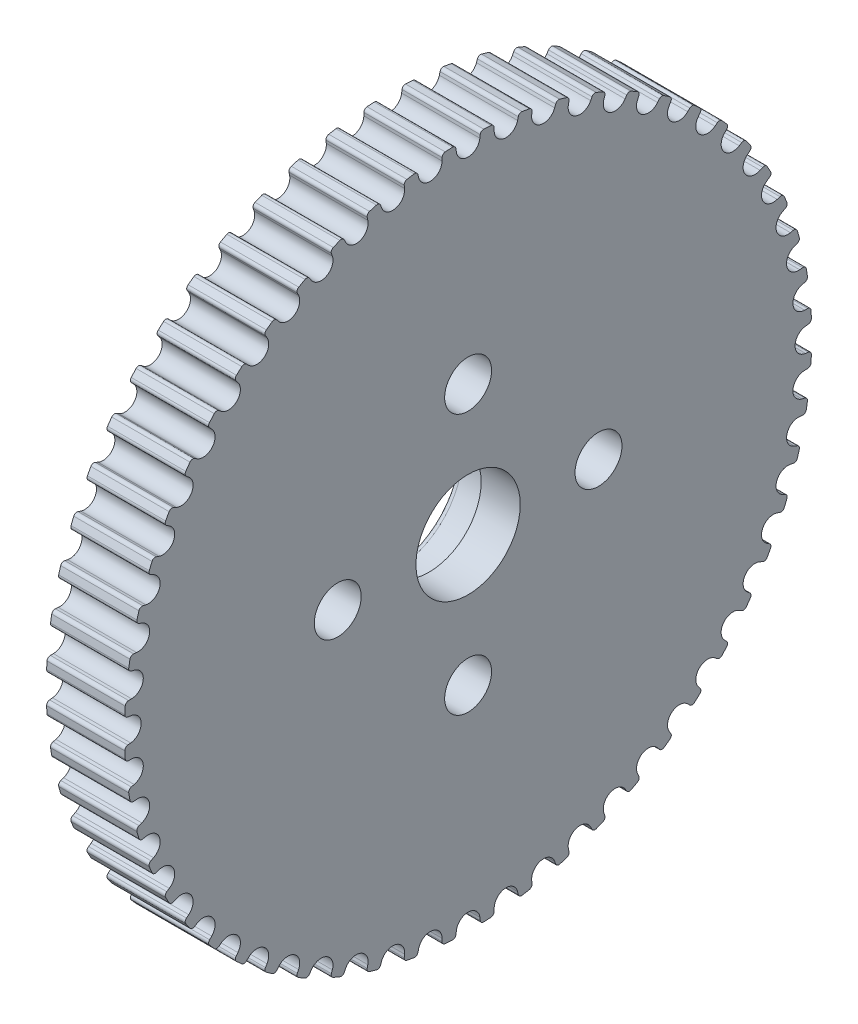
SolidWorks part; units mm, degrees
ref_plane "前视基准面" through (0, 0, 0) normal (0, 0, 1) x (1, 0, 0)
ref_plane "上视基准面" through (0, 0, 0) normal (0, 1, 0) x (1, 0, 0)
ref_plane "右视基准面" through (0, 0, 0) normal (1, 0, 0) x (0, 0, -1)
sketch "草图1" plane through (0, 0, 0) normal (0, 0, 1) x (1, 0, 0)
  line L0 (0, 0) -> (64.8368, 0) construction
  line L1 (0, 5.2718) -> (0, 26.359)
  line L2 (0, 26.359) -> (6, 26.359)
  line L3 (6, 26.359) -> (6, 10.5436)
  line L10 (6, 10.5436) -> (6, 0)
  line L11 (6, 0) -> (0, 0)
  line L12 (0, 0) -> (0, 5.2718)
  dimension "B" = 6
  dimension "da" = 52.718
revolve "旋转1" add sketch "草图1" angle 360 about L0
ref_axis "基准轴1" through (-0.45, 0, 0) along (1, 0, 0)
sketch "草图6" plane through (0, 0, 0) normal (1, 0, 0) x (0, 0, -1)
  line L0 (0, 0) -> (0, 30.6512) construction
  line L1 (0.9309, 26.1036) -> (0.9032, 25.8781)
  line L2 (1.4605, 26.3185) -> (1.6571, 27.9201)
  line L3 (-1.4605, 26.3185) -> (-1.6571, 27.9201)
  line L4 (-0.9309, 26.1036) -> (-0.9032, 25.8781)
  circle A0 centre (0, 0) radius 26.359 construction
  circle A1 centre (0, 0) radius 25.079 construction
  arc A2 (-0.9032, 25.8781) -> (0.9032, 25.8781) centre (0, 25.989) ccw
  arc A3 (1.6571, 27.9201) -> (-1.6571, 27.9201) centre (0, 0) ccw
  arc A4 (0.9309, 26.1036) -> (1.2008, 26.3316) centre (1.189, 26.0719) cw
  arc A5 (1.2008, 26.3316) -> (1.4605, 26.3185) centre (0, 0) cw
  arc A6 (-1.2008, 26.3316) -> (-1.4605, 26.3185) centre (0, 0) ccw
  arc A7 (-0.9309, 26.1036) -> (-1.2008, 26.3316) centre (-1.189, 26.0719) ccw
  point P7 (0, 1.9)
  point P8 (0, 29.3712)
  point P15 (0.9601, 26.3415)
  dimension "D1" = 50.158
  dimension "ra" = 0.26
  dimension "rf" = 0.91
  dimension "hg" = 1.28
  dimension "D3" = 0.26
  dimension "D4" = 1.6136
  dimension "angle" = 14
  dimension "bw" = 1.9
extrude "切除-拉伸2" cut sketch "草图6" along normal up to next
pattern_circular "阵列(圆周)3" count 56 over 360 about axis through (-0.45, 0, 0) along (1, 0, 0) of "切除-拉伸2"
sketch "草图7" plane through (6, 0, 0) normal (1, 0, 0) x (0, 0, -1)
  circle A0 centre (0, 0) radius 4
  dimension "D1" = 8
extrude "切除-拉伸3" cut sketch "草图7" against normal blind 10
sketch "草图8" plane through (0, 0, 0) normal (-1, 0, 0) x (0, 0, 1)
  circle A0 centre (0, 0) radius 5.05
  dimension "D1" = 10.1
extrude "切除-拉伸4" cut sketch "草图8" against normal blind 3
sketch "草图9" plane through (6, 0, 0) normal (1, 0, 0) x (0, 0, -1)
  circle A0 centre (0, 0) radius 10 construction
  circle A1 centre (0, 10) radius 1.8
  circle A2 centre (10, 0) radius 1.8
  circle A3 centre (0, -10) radius 1.8
  circle A4 centre (-10, 0) radius 1.8
  point P14 (0, 0)
  dimension "D1" = 20
  dimension "D3" = 3.6
  dimension "D2" = 4
extrude "切除-拉伸5" cut sketch "草图9" against normal blind 10
sketch "草图11" plane through (0, 0, 0) normal (-1, 0, 0) x (0, 0, 1)
  circle A0 centre (0, 10) radius 2.8
  circle A1 centre (10, 0) radius 2.8
  circle A2 centre (0, -10) radius 2.8
  circle A3 centre (-10, 0) radius 2.8
  point P12 (0, 0)
  dimension "D1" = 5.6
  dimension "D2" = 4
fillet "圆角1" radius 0.5 1 edges at (0, 0, 5.05)
chamfer "倒角1" distance 2.5 angle 45 4 edges at (0, 0, 8.2) (0, -10, -1.8) (0, 10, -1.8) (0, 0, -11.8)
equation "\"D1@草图6\" = \"da@草图1\"  - \"hg@草图6\" - \"hg@草图6\""
equation "\"D3@草图6\" = \"ra@草图6\""
